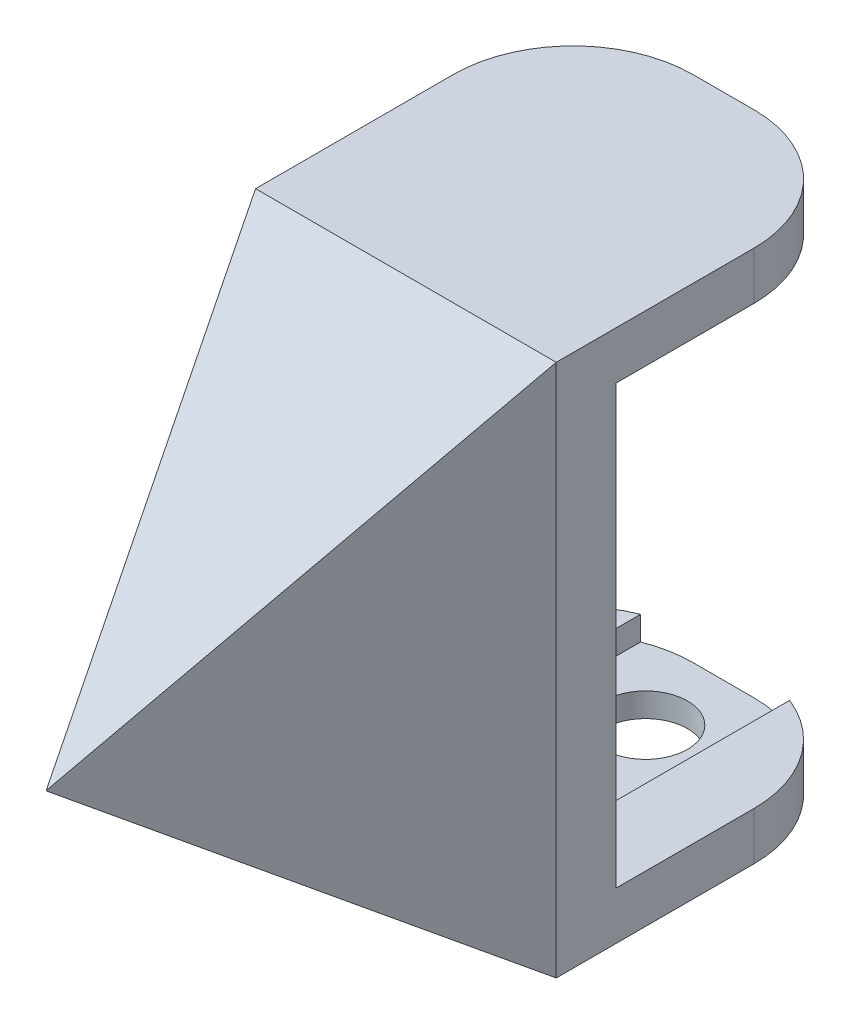
SolidWorks part; units mm, degrees
ref_plane "Front Plane" through (0, 0, 0) normal (0, 0, 1) x (1, 0, 0)
ref_plane "Top Plane" through (0, 0, 0) normal (0, 1, 0) x (1, 0, 0)
ref_plane "Right Plane" through (0, 0, 0) normal (1, 0, 0) x (0, 0, -1)
sketch "Sketch4" plane through (0, 0, 0) normal (0, 0, 1) x (1, 0, 0)
  line L1 (-6.23, -9.975) -> (6.23, -9.975)
  line L2 (-6.23, -9.975) -> (-6.23, 7.275)
  line L3 (-6.23, 7.275) -> (6.23, 7.275)
  line L4 (6.23, -9.975) -> (6.23, 7.275)
  point P4 (0, 7.275)
  dimension "D1" = 12.46
  dimension "D2" = 17.25
  dimension "D3" = 9.975
extrude "Boss-Extrude3" add sketch "Sketch4" along normal blind 6
sketch "Sketch8" plane through (0, -9.975, 0) normal (0, -1, 0) x (-1, 0, 0)
  circle A0 centre (0, -23.55) radius 12.5468
  circle A1 centre (0, -23.55) radius 11.15
  dimension "D1" = 22.3
  dimension "D2" = 23.55
extrude "Boss-Extrude6" add sketch "Sketch8" along normal blind 7.3 and the other way up to surface (17.25 mm away) other way up to face at (0, 7.275, 3)
sketch "Sketch5" plane through (0, 7.275, 0) normal (0, 1, 0) x (1, 0, 0)
  line L8 (12.5468, -23.55) -> (12.5468, 0)
  line L9 (12.5468, 0) -> (6.23, 0)
  line L10 (-12.5468, -23.55) -> (-12.5468, 0)
  line L11 (-12.5468, 0) -> (-6.23, 0)
  line L12 (-6.23, 0) -> (-6.23, -29.7)
  line L14 (6.23, -29.7) -> (6.23, 0)
  line L15 (-6.23, -29.7) -> (6.23, -29.7)
  line L16 (6.23, -6) -> (-6.23, -6) construction
  circle A0 centre (0, -23.55) radius 12.5468 construction
  arc A1 (-12.5468, -23.55) -> (12.5468, -23.55) centre (0, -23.55) ccw
  dimension "D1" = 23.7
  dimension "D2" = 23.55
extrude "Boss-Extrude4" add sketch "Sketch5" against normal up to surface (17.25 mm away) up to face at (0, -9.975, 3)
sketch "Sketch6" plane through (0, 7.275, 0) normal (0, 1, 0) x (1, 0, 0)
  line L0 (6.23, -6) -> (-6.23, -6) construction
  line L3 (6.23, -29.7) -> (-6.23, -29.7) construction
  circle A0 centre (0, -3.5) radius 2
  circle A1 centre (0, -32.2) radius 2
  dimension "D1" = 4
  dimension "D3" = 4
  dimension "D2" = 2.5
  dimension "D4" = 2.5
extrude "Cut-Extrude1" cut sketch "Sketch6" against normal blind 5
chamfer "Chamfer1" distance 0.5 angle 60 2 edges at (0, 7.275, 5.5) (0, 7.275, 34.2) first distance on face at (0, 7.275, 5.5)
sketch "Sketch10" plane through (0, 7.275, 0) normal (0, 1, 0) x (1, 0, 0)
  line L1 (-6.23, -6) -> (6.23, -6)
  line L2 (-6.23, -6) -> (-6.23, -29.7)
  line L3 (-6.23, -29.7) -> (6.23, -29.7)
  line L4 (6.23, -6) -> (6.23, -29.7)
extrude "Cut-Extrude3" cut sketch "Sketch10" against normal up to surface (17.25 mm away) up to face at (0, -9.975, 10.3399)
ref_plane "Plane1" through (0, 0, 36.0968) normal (0, 0, 1) x (1, 0, 0)
sketch "Sketch11" plane through (0, 0, 36.0968) normal (0, 0, 1) x (1, 0, 0)
  line L0 (-11.15, -9.975) -> (11.15, -9.975) construction
  line L1 (-2.5, -6.975) -> (2.5, -6.975)
  line L2 (-2.5, -6.975) -> (-2.5, -9.975)
  line L3 (-2.5, -9.975) -> (2.5, -9.975)
  line L4 (2.5, -6.975) -> (2.5, -9.975)
  point P4 (0, -6.975)
  dimension "D1" = 0
  dimension "D2" = 5
  dimension "D3" = 3
extrude "Cut-Extrude4" cut sketch "Sketch11" against normal up to next
sketch "Sketch13" plane through (0, -17.275, 0) normal (0, -1, 0) x (1, 0, 0)
  line L0 (-12.5468, 23.55) -> (-12.5468, 0)
  line L1 (-12.5468, 0) -> (12.5468, 0)
  line L2 (12.5468, 0) -> (12.5468, 23.55)
  arc A0 (-12.5468, 23.55) -> (12.5468, 23.55) centre (0, 23.55) ccw
  point P3 (0, 0)
extrude "Boss-Extrude7" add sketch "Sketch13" against normal up to surface (7.3 mm away) up to face at (0, -9.975, 10.3399)
sketch "Sketch15" plane through (0, 7.275, 0) normal (0, 1, 0) x (1, 0, 0)
  line L0 (-12.5468, 0) -> (12.5468, 0)
  line L1 (12.5468, 0) -> (12.5468, -23.55)
  line L2 (-12.5468, 0) -> (-12.5468, -23.55)
  line L3 (6.23, -6) -> (6.23, -29.7) construction
  line L4 (-6.23, -0.8) -> (6.23, -0.8)
  line L5 (-6.23, -0.8) -> (-6.23, -33.5)
  line L6 (-5.23, -34.5) -> (5.23, -34.5)
  line L7 (6.23, -0.8) -> (6.23, -33.5)
  arc A0 (-12.5468, -23.55) -> (12.5468, -23.55) centre (0, -23.55) ccw
  circle A1 centre (0, -3.5) radius 2 construction
  arc A2 (5.23, -34.5) -> (6.23, -33.5) centre (5.23, -33.5) ccw
  arc A3 (-6.23, -33.5) -> (-5.23, -34.5) centre (-5.23, -33.5) ccw
  point P15 (0, -0.8)
  dimension "D1" = 0.8
  dimension "D3" = 1
  dimension "D2" = 2.7
  dimension "D4" = 0
  dimension "D5" = 34.5
extrude "Boss-Extrude9" add sketch "Sketch15" along normal blind 10
sketch "Sketch17" plane through (-12.5468, 4.7282, 0) normal (1, 0, 0) x (0, -1, 0)
  line L0 (26.9782, 26.5) -> (26.9782, 0)
  line L1 (26.9782, 0) -> (-17.5218, 0)
  line L2 (-17.5218, 0) -> (-17.5218, 26.5)
  line L3 (-17.5218, 26.5) -> (-13.5218, 26.5)
  line L4 (-13.5218, 26.5) -> (-13.5218, 5)
  line L5 (-13.5218, 5) -> (22.9782, 5)
  line L6 (22.9782, 5) -> (22.9782, 26.5)
  line L7 (22.9782, 26.5) -> (26.9782, 26.5)
  point P2 (4.7282, 5)
  point P10 (4.7282, 0)
  dimension "D1" = 4
  dimension "D2" = 36.5
  dimension "D3" = 0
  dimension "D4" = 26.5
  dimension "D5" = 5
extrude "Boss-Extrude10" add sketch "Sketch17" along normal up to surface (25.0936 mm away) up to face at (12.5468, 0, 11.775)
sketch "Sketch18" plane through (0, -18.25, 0) normal (0, 1, 0) x (0, 0, 1)
  line L0 (-26.5, -12.5468) -> (-26.5, 12.5468) construction
  line L1 (-26.5, 6.2191) -> (-5, 6.2191)
  line L2 (-26.5, 6.2191) -> (-26.5, -6.2191)
  line L3 (-26.5, -6.2191) -> (-5, -6.2191)
  line L4 (-5, 6.2191) -> (-5, -6.2191)
  line L5 (-5, -12.5468) -> (-5, 12.5468) construction
  point P6 (-26.5, 0)
  point P7 (-26.5, 0)
  dimension "D1" = 0
extrude "Cut-Extrude5" cut sketch "Sketch18" against normal blind 2
sketch "Sketch19" plane through (0, -20.25, 0) normal (0, 1, 0) x (0, 0, 1)
  line L0 (-26.5, -12.5468) -> (-26.5, 12.5468) construction
  circle A0 centre (-20, 0) radius 3.5
  dimension "D1" = 7
  dimension "D2" = 6.5
extrude "Cut-Extrude6" cut sketch "Sketch19" against normal through all both and the other way through all
fillet "Fillet1" radius 10 4 edges at (12.5468, -20.25, -26.5) (-12.5468, -20.25, -26.5) (-12.5468, 20.25, -26.5) (12.5468, 20.25, -26.5)
ref_plane "Plane2" through (0, 0, 0) normal (1, 0, 0) x (0, 0, -1)
ref_plane "Plane3" through (0, 0, 0) normal (0, -1, 0) x (-1, 0, 0)
sketch "Sketch20" plane through (0, 17.275, 0) normal (0, 1, 0) x (1, 0, 0)
  line L1 (12.5468, 0) -> (-12.5468, 0)
  line L2 (12.5468, 0) -> (12.5468, -36.0968)
  line L3 (12.5468, -36.0968) -> (-12.5468, -36.0968)
  line L4 (-12.5468, 0) -> (-12.5468, -36.0968)
extrude "Cut-Extrude7" cut sketch "Sketch20" against normal through all both and the other way through all
sketch "Sketch21" plane through (0, 22.25, 0) normal (0, 1, 0) x (1, 0, 0)
  line L0 (12.5468, 0) -> (-0.0254, -30)
  line L1 (-0.0254, -30) -> (-12.5468, 0)
  line L2 (-12.5468, 0) -> (12.5468, 0)
  dimension "D1" = 30
extrude "Boss-Extrude11" add sketch "Sketch21" against normal up to vertex (44.5 mm away) up to point (-12.5468, -22.25, 0)
sketch "Sketch22" plane through (0, 0, 0) normal (1, 0, 0) x (0, 0, -1)
  line L13 (0, 22.25) -> (-30, 0.01)
  line L14 (-30, -22.25) -> (-30, 22.25) construction
  line L15 (-30, 0.01) -> (-30, 22.25)
  line L16 (-30, 22.25) -> (0, 22.25)
  line L17 (0, -22.25) -> (-30, -22.25)
  line L18 (-30, -22.25) -> (-30, -0.01)
  line L19 (-30, -0.01) -> (0, -22.25)
  dimension "D1" = 0.02
  dimension "D2" = 0.01
extrude "Cut-Extrude8" cut sketch "Sketch22" against normal through all both and the other way through all
sketch "Sketch23" plane through (0, 0, 0) normal (0, 0, -1) x (-1, 0, 0)
  line L0 (12.5468, 18.25) -> (0, 0)
  line L1 (0, 0) -> (12.5468, -22.25)
  line L2 (12.5468, -22.25) -> (12.5468, 18.25)
extrude "Cut-Extrude9" cut sketch "Sketch23" against normal through all both and the other way through all
sketch "Sketch24" plane through (0, 22.25, 0) normal (0, 1, 0) x (1, 0, 0)
  circle A0 centre (0, 20) radius 6.5
  dimension "D1" = 13
extrude "Boss-Extrude12" add sketch "Sketch24" against normal blind 5
sketch "Sketch25" plane through (0, 17.25, 0) normal (0, -1, 0) x (1, 0, 0)
  circle A0 centre (0, -20) radius 5.85
  dimension "D1" = 11.7
extrude "Boss-Extrude13" add sketch "Sketch25" along normal blind 5
fillet "Fillet2" radius 1 1 edges at (0, 12.25, -25.85)
